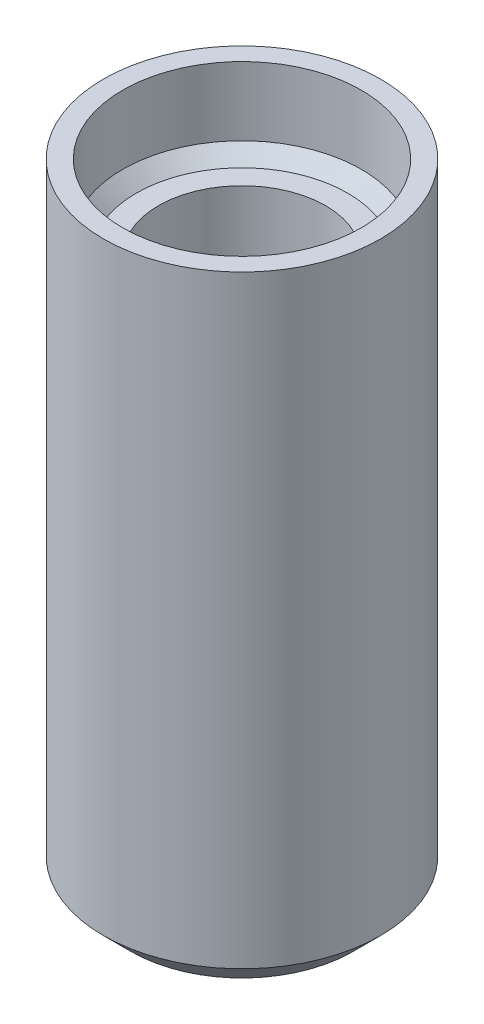
SolidWorks part; units mm, degrees
ref_plane "Front Plane" through (0, 0, 0) normal (0, 0, 1) x (1, 0, 0)
ref_plane "Top Plane" through (0, 0, 0) normal (0, 1, 0) x (1, 0, 0)
ref_plane "Right Plane" through (0, 0, 0) normal (1, 0, 0) x (0, 0, -1)
sketch "Sketch1" plane through (0, 0, 0) normal (0, 1, 0) x (1, 0, 0)
  line L0 (-2.5652, -1.65) -> (2.5652, -1.65)
  circle A0 centre (0, 0) radius 3.05
  circle A1 centre (0, 0) radius 5.05
  dimension "D1" = 6.1
  dimension "D3" = 1.65
  dimension "D2" = 2
extrude "Boss-Extrude1" add sketch "Sketch1" along normal blind 20 contours A1 A0 | L0 A0 region at (0, 0, 2.2227) region at (-4.9072, 0, 0)
sketch "Sketch2" plane through (0, 0, 0) normal (0, -1, 0) x (1, 0, 0)
  circle A1 centre (0, 0) radius 5.05
  circle A2 centre (0, 0) radius 5.05
  dimension "D1" = 0
extrude "Boss-Extrude2" add sketch "Sketch2" against normal blind 2
sketch "Sketch4" plane through (0, 20, 0) normal (0, 1, 0) x (1, 0, 0)
  circle A0 centre (0, 0) radius 4.35
  circle A1 centre (0, 0) radius 5.05
  circle A2 centre (0, 0) radius 5.05
  dimension "D1" = 0
  dimension "D2" = 0.7
extrude "Boss-Extrude3" add sketch "Sketch4" along normal blind 3
chamfer "Chamfer1" distance 1 angle 45 1 edges at (0, 0, 5.05)
chamfer "Chamfer2" distance 0.5 angle 45 1 edges at (0, 20, 4.35)
sketch "Sketch5" plane through (0, 0, 0) normal (0, -1, 0) x (1, 0, 0)
  line L0 (-1.326, 0) -> (1.326, 0) construction
  line L1 (-3.5217, -2) -> (3.5217, -2) construction
  circle A0 centre (0, 0) radius 4.05 construction
  text T0 "<b>6</b>" font "Calibri" height in points 16
  dimension "D1" = 2
extrude "Cut-Extrude1" cut sketch "Sketch5" against normal blind 0.4
extrude "Boss-Extrude4" add sketch "Sketch5<2>" against normal blind 0.4 separate body
sketch "Sketch5<2>" plane through (0, 0, 0) normal (0, -1, 0) x (1, 0, 0) same geometry as "Sketch5"
equation "\"ID\"= 6.3"
equation "\"notch\"= 6.3 / 2 - 1.5"
equation "\"D3@Sketch1\"=\"notch\""
